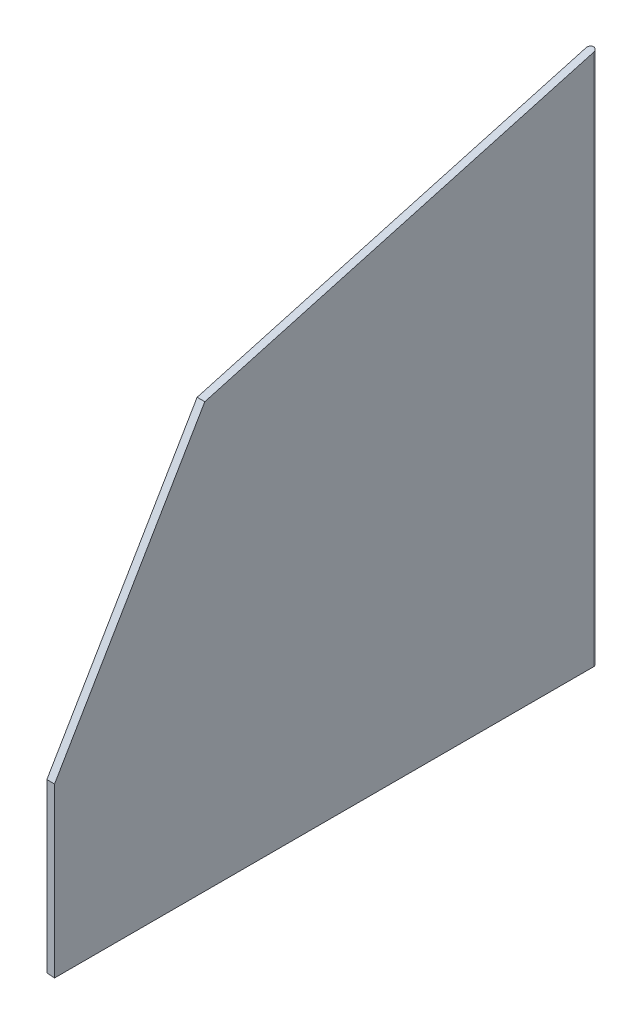
SolidWorks part; units mm, degrees
material "Verre"
ref_plane "Plan de face" through (0, 0, 0) normal (0, 0, 1) x (1, 0, 0)
ref_plane "Plan de dessus" through (0, 0, 0) normal (0, 1, 0) x (1, 0, 0)
ref_plane "Plan de droite" through (0, 0, 0) normal (1, 0, 0) x (0, 0, -1)
sketch "Esquisse1" plane through (0, 0, 0) normal (1, 0, 0) x (0, 0, -1)
  line L0 (635.7096, 813.7456) -> (-385.4717, 529.5119)
  line L1 (-385.4717, 529.5119) -> (-776.2904, -136.2544)
  line L2 (-776.2904, -136.2544) -> (-776.2904, -573.2544)
  line L3 (-776.2904, -573.2544) -> (635.7096, -573.2544)
  line L4 (635.7096, -573.2544) -> (635.7096, 813.7456)
  dimension "D1" = 1387
  dimension "D2" = 1412
  dimension "D3" = 437
  dimension "D4" = 772
  dimension "D5" = 1060
extrude "Boss.-Extru.1" add sketch "Esquisse1" along normal blind 20
sketch "Esquisse4" plane through (0, 0, 0) normal (0, 0, 1) x (1, 0, 0)
  line L0 (0, -573.2544) -> (0, -571.9225)
  line L1 (0, -136.2544) -> (0, -573.2544) construction
  line L2 (0, -571.9225) -> (20, -573.2544)
  line L3 (20, -573.2544) -> (0, -573.2544)
  dimension "D1" = 3.81
extrude "Enlèv. mat.-Extru.1" cut sketch "Esquisse4" against normal blind 792 and the other way blind 871
sketch "Esquisse5" plane through (-37.9191, -569.3973, 0) normal (-0.0664, -0.9978, 0) x (0.9978, -0.0664, 0)
  line L0 (38.0031, -635.7096) -> (58.0474, -635.7096) construction
  line L1 (58.0474, 776.2904) -> (58.0474, -635.7096) construction
  circle A0 centre (48.0274, -625.7096) radius 5
  dimension "D1" = 10
  dimension "D2" = 10.02
extrude "Enlèv. mat.-Extru.2" cut sketch "Esquisse5" against normal blind 20
fillet "Congé1" radius 10 2 edges at (0, 120.9115, -635.7096) (20, 120.2456, -635.7096)
